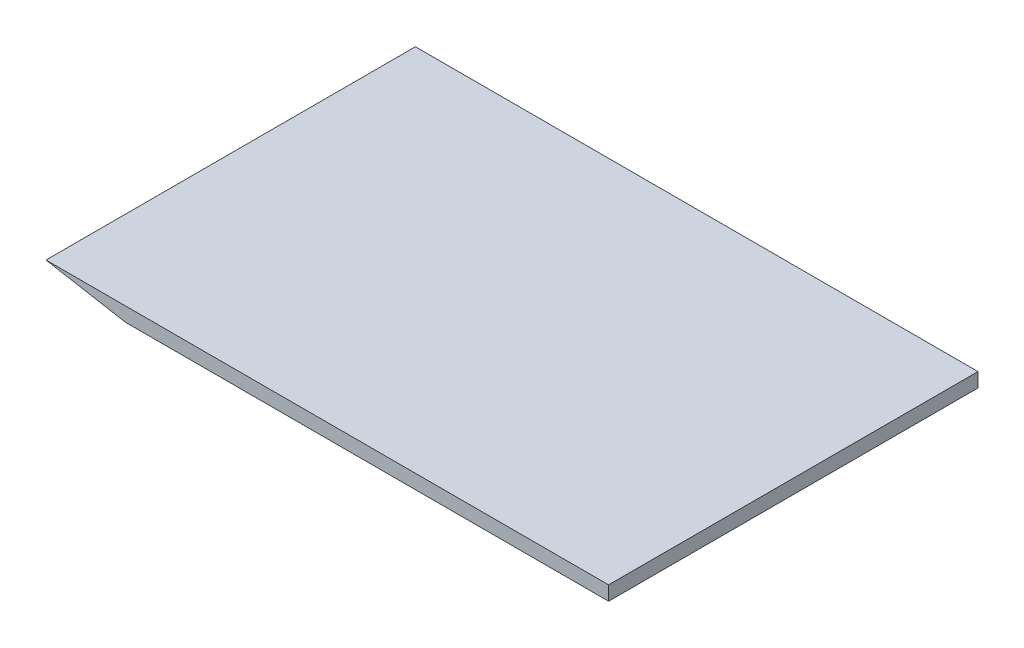
SolidWorks part; units mm, degrees
ref_plane "Front Plane" through (0, 0, 0) normal (0, 0, 1) x (1, 0, 0)
ref_plane "Top Plane" through (0, 0, 0) normal (0, 1, 0) x (1, 0, 0)
ref_plane "Right Plane" through (0, 0, 0) normal (1, 0, 0) x (0, 0, -1)
sketch "Sketch1" plane through (0, 0, 0) normal (0, 0, 1) x (1, 0, 0)
  line L0 (0, 0) -> (198, 0)
  line L1 (198, 0) -> (198, -5)
  line L2 (198, -5) -> (28, -5)
  line L3 (28, -5) -> (0, 0)
  dimension "D1" = 5
  dimension "D2" = 170
  dimension "D3" = 28
extrude "Boss-Extrude1" add sketch "Sketch1" along normal blind 130 contours L3 L0 L1 L2
